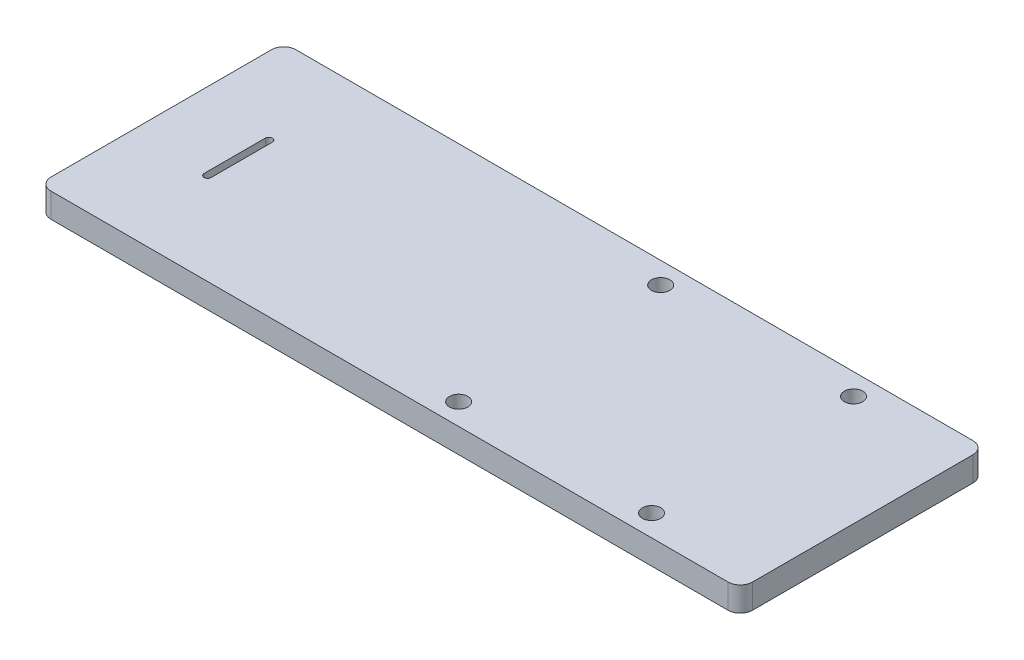
SolidWorks part; units mm, degrees
material "6061 Alloy"
ref_plane "Front Plane" through (0, 0, 0) normal (0, 0, 1) x (1, 0, 0)
ref_plane "Top Plane" through (0, 0, 0) normal (0, 1, 0) x (1, 0, 0)
ref_plane "Right Plane" through (0, 0, 0) normal (1, 0, 0) x (0, 0, -1)
sketch "Sketch1" plane through (0, 0, 0) normal (0, 1, 0) x (1, 0, 0)
  line L1 (-181.9, -63.5) -> (181.9, -63.5)
  line L2 (-181.9, -63.5) -> (-181.9, 63.5)
  line L3 (-181.9, 63.5) -> (181.9, 63.5)
  line L4 (181.9, -63.5) -> (181.9, 63.5)
  line L5 (-181.9, -63.5) -> (181.9, 63.5) construction
  line L6 (-181.9, 63.5) -> (181.9, -63.5) construction
  point P0 (0, 0)
  dimension "D1" = 127
  dimension "D2" = 363.8
extrude "Boss-Extrude1" add sketch "Sketch1" along normal blind 12.7
fillet "Fillet1" radius 6.35 4 edges at (-181.9, 6.35, -63.5) (181.9, 6.35, -63.5) (181.9, 6.35, 63.5) (-181.9, 6.35, 63.5)
sketch "Sketch2" plane through (0, 12.7, 0) normal (0, 1, 0) x (1, 0, 0)
  line L0 (-181.9, 0) -> (181.9, 0) construction
  line L3 (-181.9, 57.15) -> (-181.9, -57.15) construction
  line L4 (181.9, -57.15) -> (181.9, 57.15) construction
  line L5 (0, 63.5) -> (0, -63.5) construction
  line L6 (175.55, 63.5) -> (-175.55, 63.5) construction
  line L7 (-175.55, -63.5) -> (175.55, -63.5) construction
  circle A0 centre (24.73, 52.3748) radius 4.7752
  circle A1 centre (24.73, -52.3748) radius 4.7752
  circle A2 centre (124.75, -52.3748) radius 4.7752
  circle A3 centre (124.75, 52.3748) radius 4.7752
  point P14 (24.73, 57.15)
  point P15 (0, 0)
  point P22 (0, 0)
  dimension "D1" = 100.02
  dimension "D4" = 9.5504
  dimension "D2" = 6.35
  dimension "D3" = 57.15
  dimension "D5" = 57.15
extrude "Cut-Extrude1" cut sketch "Sketch2" against normal through all
sketch "Sketch3" plane through (0, 0, 0) normal (0, -1, 0) x (1, 0, 0)
  line L0 (-141.9753, 15.875) -> (-141.9753, -15.875) construction
  line L2 (-140.1464, 15.875) -> (-140.1464, -15.875)
  line L3 (-143.8041, 15.875) -> (-143.8041, -15.875)
  line L4 (-181.9, 0) -> (181.9, 0) construction
  line L5 (-181.9, -57.15) -> (-181.9, 57.15) construction
  line L6 (181.9, 57.15) -> (181.9, -57.15) construction
  arc A0 (-140.1464, 15.875) -> (-143.8041, 15.875) centre (-141.9753, 15.875) ccw
  arc A1 (-143.8041, -15.875) -> (-140.1464, -15.875) centre (-141.9753, -15.875) ccw
  point P4 (-141.9753, 0)
  dimension "D1" = 0
  dimension "D2" = 31.75
extrude "Cut-Extrude2" cut sketch "Sketch3" against normal up to next
